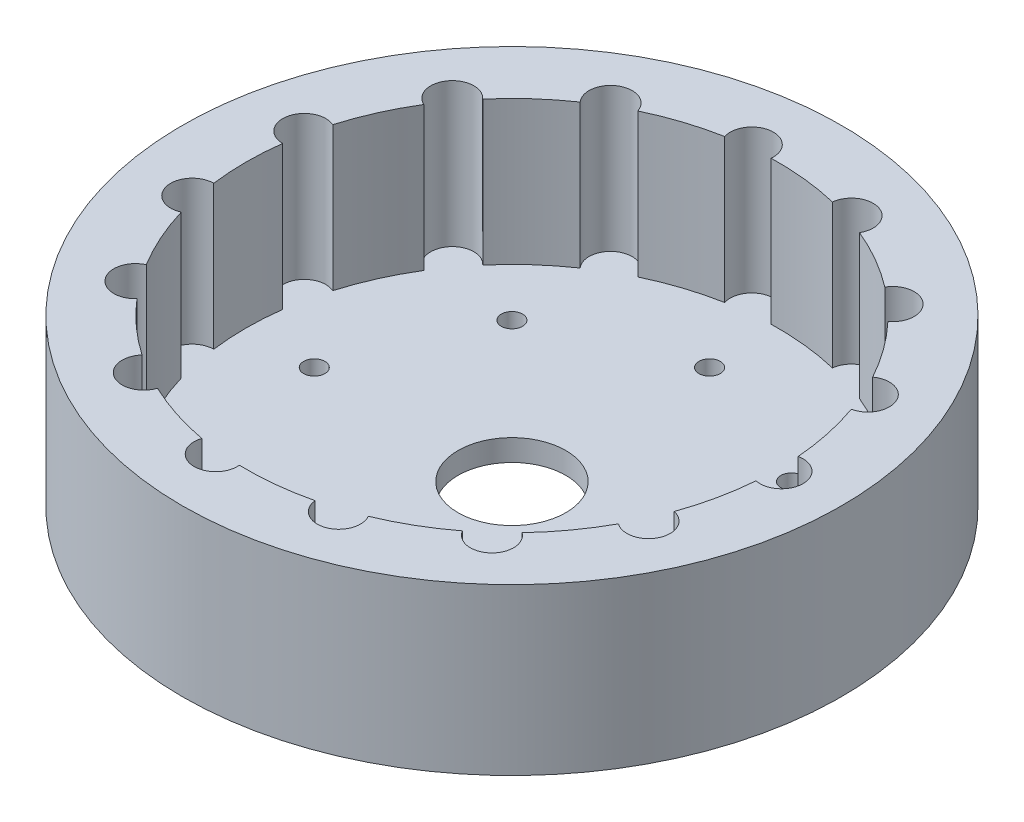
SolidWorks part; units mm, degrees
ref_plane "Front Plane" through (0, 0, 0) normal (0, 0, 1) x (1, 0, 0)
ref_plane "Top Plane" through (0, 0, 0) normal (0, 1, 0) x (1, 0, 0)
ref_plane "Right Plane" through (0, 0, 0) normal (1, 0, 0) x (0, 0, -1)
sketch "Sketch1" plane through (0, 0, 0) normal (0, 1, 0) x (1, 0, 0)
  circle A0 centre (0, 0) radius 7.5
  circle A1 centre (0, 0) radius 45.85
  circle A2 centre (0, 0) radius 37.5 construction
  circle A3 centre (37.5, 0) radius 3
  circle A4 centre (34.258, 15.2526) radius 3
  circle A5 centre (25.0924, 27.8679) radius 3
  circle A6 centre (11.5881, 35.6646) radius 3
  circle A7 centre (-3.9198, 37.2946) radius 3
  circle A8 centre (-18.75, 32.476) radius 3
  circle A9 centre (-30.3381, 22.0419) radius 3
  circle A10 centre (-36.6805, 7.7967) radius 3
  circle A11 centre (-36.6805, -7.7967) radius 3
  circle A12 centre (-30.3381, -22.0419) radius 3
  circle A13 centre (-18.75, -32.476) radius 3
  circle A14 centre (-3.9198, -37.2946) radius 3
  circle A15 centre (11.5881, -35.6646) radius 3
  circle A16 centre (25.0924, -27.8679) radius 3
  circle A17 centre (34.258, -15.2526) radius 3
  circle A19 centre (0, 0) radius 27.5 construction
  circle A20 centre (27.5, 0) radius 1.48
  circle A21 centre (19.4454, -19.4454) radius 1.48
  circle A22 centre (0, -27.5) radius 1.48
  circle A23 centre (-19.4454, -19.4454) radius 1.48
  circle A24 centre (-27.5, 0) radius 1.48
  circle A25 centre (-19.4454, 19.4454) radius 1.48
  circle A26 centre (0, 27.5) radius 1.48
  circle A27 centre (19.4454, 19.4454) radius 1.48
  arc A28 (36.8833, 2.9359) -> (34.8888, 12.3197) centre (0, 0) ccw
  arc A29 (34.8888, -12.3197) -> (36.8833, -2.9359) centre (0, 0) ccw
  arc A30 (26.8616, -25.4451) -> (32.5004, -17.6839) centre (0, 0) ccw
  arc A31 (14.1898, -34.1709) -> (22.4979, -29.3742) centre (0, 0) ccw
  arc A32 (-0.9355, -36.9882) -> (8.6053, -35.9854) centre (0, 0) ccw
  arc A33 (-15.8991, -33.4099) -> (-6.7752, -36.3744) centre (0, 0) ccw
  arc A34 (-28.1135, -24.0547) -> (-20.9843, -30.4739) centre (0, 0) ccw
  arc A35 (-35.4669, -10.5403) -> (-31.5649, -19.3043) centre (0, 0) ccw
  arc A36 (-36.6878, 4.7967) -> (-36.6878, -4.7967) centre (0, 0) ccw
  arc A37 (-31.5649, 19.3043) -> (-35.4669, 10.5403) centre (0, 0) ccw
  arc A38 (-20.9843, 30.4739) -> (-28.1135, 24.0547) centre (0, 0) ccw
  arc A39 (-6.7752, 36.3744) -> (-15.8991, 33.4099) centre (0, 0) ccw
  arc A40 (8.6053, 35.9854) -> (-0.9355, 36.9882) centre (0, 0) ccw
  arc A41 (22.4979, 29.3742) -> (14.1898, 34.1709) centre (0, 0) ccw
  arc A42 (32.5004, 17.6839) -> (26.8616, 25.4451) centre (0, 0) ccw
  point P38 (0, 0)
  point P57 (0, 0)
  point P87 (0, 0)
  dimension "D2" = 15
  dimension "D3" = 75
  dimension "D4" = 91.7
  dimension "D5" = 6
  dimension "D8" = 2.96
  dimension "D9" = 55
  dimension "D6" = 37
  dimension "D1" = 15
  dimension "D7" = 8
  dimension "D10" = 15
extrude "Boss-Extrude1" add sketch "Sketch1" against normal blind 3 contours A4 A42 A5 A41 A6 A40 A7 A39 A8 A38 A9 A37 A10 A36 A11 A35 A12 A34 A13 A33 A14 A32 A15 A31 A16 A30 A17 A29 A3 A28 A0 A20 A21 A22 A23 A24 A25 A26 A27 | A3 | A17 | A4 | A5 | A6 | A7 | A8 | A9 | A10 | A11 | A12 | A13 | A14 | A15 | A16 | A1 A42 A4 A28 A3 A29 A17 A30 A16 A31 A15 A32 A14 A33 A13 A34 A12 A35 A11 A36 A10 A37 A9 A38 A8 A39 A7 A40 A6 A41 A5 | A22 | A23 | A24 | A25 | A26 | A27 | A20 | A21 region at (-44.5532, 0, 0) region at (37.5, 0, 0) region at (33.4543, 0, 0) region at (34.258, 0, -15.2526) region at (34.258, 0, 15.2526) region at (25.0924, 0, -27.8679) region at (25.0924, 0, 27.8679) region at (11.5881, 0, -35.6646) region at (11.5881, 0, 35.6646) region at (-3.9198, 0, -37.2946) region at (-3.9198, 0, 37.2946) region at (-18.75, 0, -32.476) region at (-18.75, 0, 32.476) region at (-30.3381, 0, -22.0419) region at (-30.3381, 0, 22.0419) region at (-36.6805, 0, -7.7967) region at (-36.6805, 0, 7.7967) region at (27.5, 0, 0) region at (19.4454, 0, 19.4454) region at (0, 0, 27.5) region at (-19.4454, 0, 19.4454) region at (-27.5, 0, 0) region at (-19.4454, 0, -19.4454) region at (0, 0, -27.5) region at (19.4454, 0, -19.4454)
extrude "Cut-Extrude1" cut sketch "Sketch1<6>" against normal blind 2.22 contours A24 | A25 | A26 | A27 | A20 | A21 | A22 | A23 region at (27.5, 0, 0) region at (19.4454, 0, 19.4454) region at (0, 0, 27.5) region at (-19.4454, 0, 19.4454) region at (-27.5, 0, 0) region at (-19.4454, 0, -19.4454) region at (0, 0, -27.5) region at (19.4454, 0, -19.4454)
sketch "Sketch1<6>" plane through (0, 0, 0) normal (0, 1, 0) x (1, 0, 0) same geometry as "Sketch1"
extrude "Boss-Extrude2" add sketch "Sketch1<7>" along normal blind 20 contours A1 A42 A4 A28 A3 A29 A17 A30 A16 A31 A15 A32 A14 A33 A13 A34 A12 A35 A11 A36 A10 A37 A9 A38 A8 A39 A7 A40 A6 A41 A5 region at (-44.5532, 0, 0)
sketch "Sketch1<7>" plane through (0, 0, 0) normal (0, 1, 0) x (1, 0, 0) same geometry as "Sketch1"
equation "\"bearing_21_OD\"= 21mm"
equation "\"D2@Sketch1\"=\"bearing_15_OD\"+\"bearing_21_outer_clearance\""
equation "\"pin_cirlce_diameter\" = 75mm"
equation "\"D3@Sketch1\"=\"pin_cirlce_diameter\""
equation "\"pin_diam\" = 6mm"
equation "\"D5@Sketch1\"=\"pin_diam\""
equation "\"gear_thickness\" = 4mm"
equation "\"ball_bearing_diam\"= 2.96mm"
equation "\"bearing_21_outer_clearance\"= 0mm'change this"
equation "\"bearing_15_OD\"= 15mm"
equation "\"bearing_15_outer_clearance\"= 0mm'change this"
equation "\"D8@Sketch1\"=\"ball_bearing_diam\""
equation "\"D1@Cut-Extrude1\"=\"ball_bearing_diam\"*0.75"
